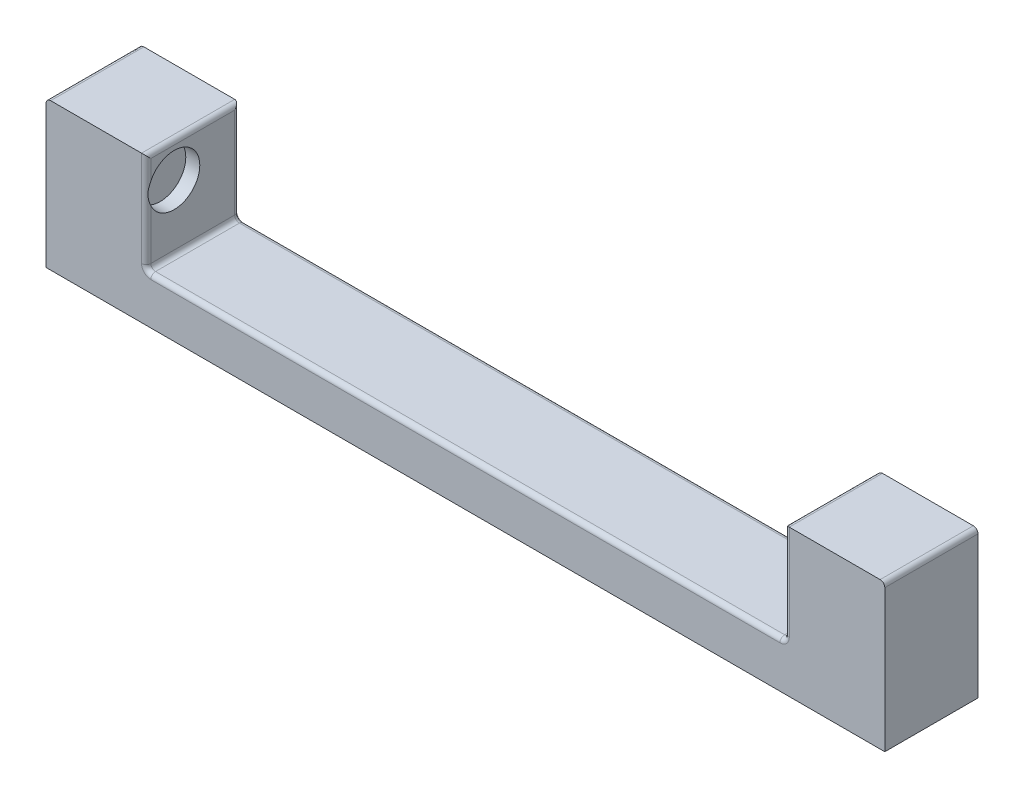
SolidWorks part; units mm, degrees
material "Plastique personnalisé"
ref_plane "Plan de face" through (0, 0, 0) normal (0, 0, 1) x (1, 0, 0)
ref_plane "Plan de dessus" through (0, 0, 0) normal (0, 1, 0) x (1, 0, 0)
ref_plane "Plan de droite" through (0, 0, 0) normal (1, 0, 0) x (0, 0, -1)
sketch "Esquisse1" plane through (0, 0, 0) normal (0, 0, 1) x (1, 0, 0)
  line L0 (0, -55) -> (0, 55) construction
  line L1 (-34.25, 10.75) -> (-45, 10.75)
  line L2 (-34.25, 10.75) -> (-34.25, 0)
  line L3 (-34.25, 0) -> (-45, 0)
  line L4 (-45, 10.75) -> (-45, 0)
  line L5 (34.25, 0) -> (45, 0)
  line L6 (45, 10.75) -> (45, 0)
  line L7 (34.25, 10.75) -> (45, 10.75)
  line L8 (34.25, 10.75) -> (34.25, 0)
  dimension "D1" = 10.75
  dimension "D2" = 34.25
extrude "Boss.-Extru.1" add sketch "Esquisse1" along normal blind 10
sketch "Esquisse3" plane through (0, 0, 0) normal (0, -1, 0) x (1, 0, 0)
  line L1 (-45, 10) -> (45, 10)
  line L2 (-45, 10) -> (-45, 0)
  line L3 (-45, 0) -> (45, 0)
  line L4 (45, 10) -> (45, 0)
extrude "Boss.-Extru.2" add sketch "Esquisse3" along normal blind 5
sketch "Esquisse4" plane through (-34.25, 0, 0) normal (1, 0, 0) x (0, 0, -1)
  line L3 (-10, 0) -> (0, 0) construction
  line L4 (0, 0) -> (0, 10.75) construction
  circle A0 centre (-7, 7) radius 2.75
  dimension "D1" = 5.5
  dimension "D2" = 7
  dimension "D3" = 7
extrude "Enlèv. mat.-Extru.1" cut sketch "Esquisse4" against normal blind 1.5
mirror "Symétrie1" about plane through (0, 0, 0) normal (1, 0, 0) of "Enlèv. mat.-Extru.1"
fillet "Congé1" radius 0.5 12 edges at (-34.25, 5.375, 0) (-34.25, 5.375, 10) (34.25, 5.375, 0) (34.25, 5.375, 10) (0, 0, 0) (0, 0, 10) (45, 10.75, 5) (34.25, 10.75, 5) (34.25, 0, 5) (-45, 10.75, 5) (-34.25, 10.75, 5) (-34.25, 0, 5)
